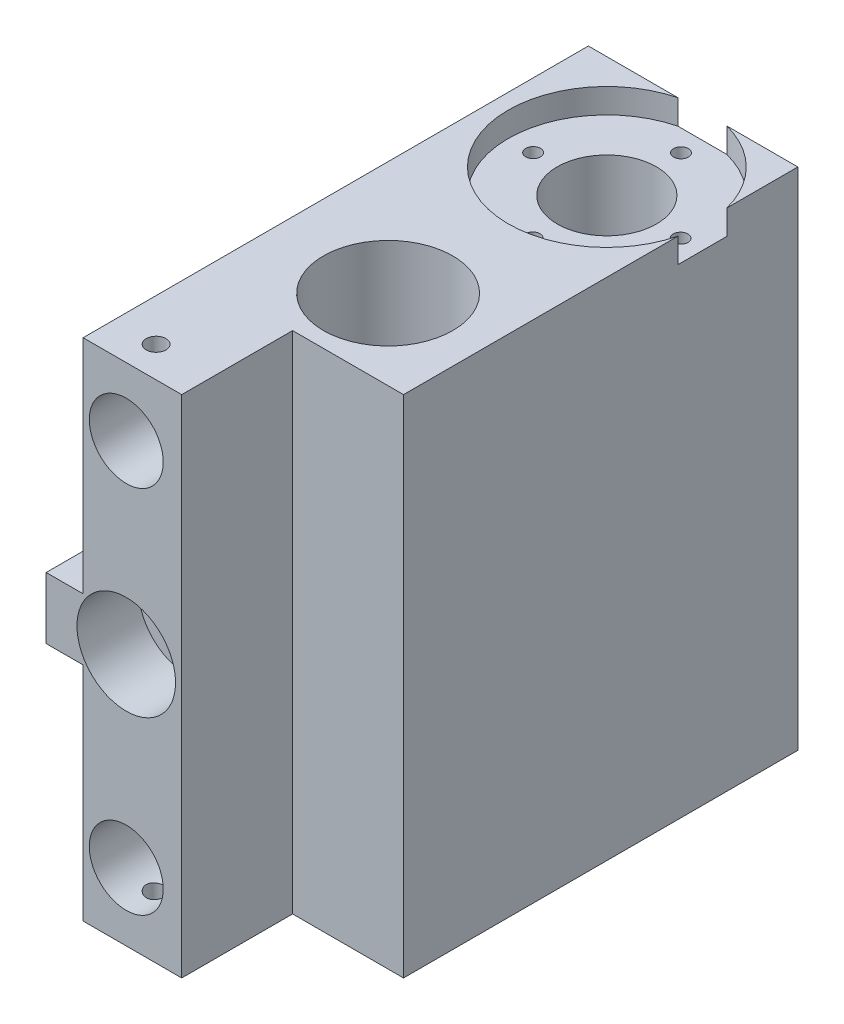
SolidWorks part; units mm, degrees
material "1060 Alloy"
ref_plane "Front Plane" through (0, 0, 0) normal (0, 0, 1) x (1, 0, 0)
ref_plane "Top Plane" through (0, 0, 0) normal (0, 1, 0) x (1, 0, 0)
ref_plane "Right Plane" through (0, 0, 0) normal (1, 0, 0) x (0, 0, -1)
sketch "Sketch1" plane through (0, 0, 0) normal (0, 0, 1) x (1, 0, 0)
  line L0 (-27, -6.0963) -> (-27, -75.9037) construction
  line L1 (0, 0) -> (-40, 0)
  line L2 (0, 0) -> (0, -82)
  line L3 (0, -82) -> (-40, -82)
  line L4 (-40, 0) -> (-40, -82)
  circle A0 centre (-27, -41) radius 5.5
  circle A1 centre (-27, -11) radius 6
  circle A2 centre (-27, -71) radius 6
  dimension "D3" = 11
  dimension "D4" = 12
  dimension "D5" = 12
  dimension "D1" = 40
  dimension "D2" = 82
  dimension "D6" = 11
  dimension "D7" = 30
  dimension "D8" = 13
  dimension "D9" = 30
  dimension "D10" = 11
extrude "Boss-Extrude1" add sketch "Sketch1" along normal blind 12
sketch "Sketch2" plane through (0, 0, 0) normal (0, 0, -1) x (-1, 0, 0)
  line L0 (0, -82) -> (0, 0) construction
  line L1 (40, -82) -> (0, -82) construction
  line L2 (40, 0) -> (40, -82) construction
  line L3 (0, 0) -> (40, 0) construction
  line L4 (0, -82) -> (0, 0)
  line L5 (40, -82) -> (0, -82)
  line L6 (40, 0) -> (40, -82)
  line L7 (0, 0) -> (40, 0)
  circle A0 centre (27, -41) radius 5.5 construction
  circle A1 centre (27, -41) radius 5.5
extrude "Boss-Extrude2" add sketch "Sketch2" along normal blind 70
sketch "Sketch3" plane through (0, 0, 0) normal (0, 1, 0) x (1, 0, 0)
  line L0 (-40, -5) -> (0, -5) construction
  line L1 (-40, -12) -> (-40, 70) construction
  line L2 (0, -12) -> (0, 70) construction
  line L3 (0, -12) -> (-40, -12) construction
  circle A0 centre (-27.1548, -7) radius 1.6
  dimension "D1" = 3.2
  dimension "D2" = 5
  dimension "D3" = 13
extrude "Cut-Extrude1" cut sketch "Sketch3" against normal blind 10
sketch "Sketch4" plane through (0, -82, 0) normal (0, -1, 0) x (1, 0, 0)
  circle A1 centre (-27.1548, 7) radius 1.6
  circle A2 centre (-27.1548, 7) radius 1.6
  dimension "D1" = 0
extrude "Cut-Extrude2" cut sketch "Sketch4" against normal blind 10
sketch "Sketch5" plane through (0, 0, 0) normal (0, 1, 0) x (1, 0, 0)
  line L0 (-15.5, 70) -> (-15.5, 49) construction
  line L1 (-40, 70) -> (0, 70) construction
  line L2 (0, -12) -> (-40, -12) construction
  line L3 (0, -12) -> (0, 70) construction
  line L4 (-15.5, 60) -> (-15.5, 49) construction
  line L5 (-15.5, 29.5) -> (-15.5, -12) construction
  line L6 (-15.5, 29.5) -> (-15.5, 8.5) construction
  circle A1 centre (-15.5, 19) radius 10.5
  circle A2 centre (-15.5, 54.5) radius 5.5
  dimension "D2" = 11
  dimension "D3" = 25
  dimension "D4" = 21
  dimension "D1" = 15.5
  dimension "D6" = 51
extrude "Cut-Extrude3" cut sketch "Sketch5" against normal blind 100
sketch "Sketch6" plane through (0, 0, 0) normal (0, 1, 0) x (1, 0, 0)
  circle A0 centre (-15.5, 54.5) radius 16
  dimension "D1" = 32
extrude "Cut-Extrude4" cut sketch "Sketch6" against normal blind 4
sketch "Sketch19" plane through (0, -4, 0) normal (0, 1, 0) x (1, 0, 0)
  circle A0 centre (-15.5, 54.5) radius 8.05
  dimension "D1" = 16.1
extrude "Cut-Extrude17" cut sketch "Sketch19" against normal blind 16
sketch "Sketch12" plane through (0, -4, 0) normal (0, 1, 0) x (1, 0, 0)
  line L1 (-3.5, 54.4698) -> (-3.4699, 66.4698) construction
  line L2 (-3.4699, 66.4698) -> (-15.4698, 66.5) construction
  line L3 (-27.5, 54.5302) -> (-27.5301, 42.5302) construction
  line L4 (-27.5301, 42.5302) -> (-15.5302, 42.5) construction
  circle A0 centre (-15.5, 54.5) radius 12 construction
  circle A1 centre (-15.5302, 42.5) radius 1.2
  circle A2 centre (-3.5, 54.4698) radius 1.2
  circle A3 centre (-15.4698, 66.5) radius 1.2
  circle A4 centre (-27.5, 54.5302) radius 1.2
  dimension "D1" = 24
  dimension "D2" = 2.4
extrude "Cut-Extrude12" cut sketch "Sketch12" against normal blind 12
sketch "Sketch13" plane through (0, 0, -70) normal (0, 0, -1) x (-1, 0, 0)
  line L1 (40, 0) -> (60, 0)
  line L2 (40, 0) -> (40, -70)
  line L3 (40, -70) -> (60, -70)
  line L4 (60, 0) -> (60, -70)
  dimension "D1" = 20
  dimension "D2" = 70
extrude "Boss-Extrude3" add sketch "Sketch13" against normal blind 30
sketch "Sketch14" plane through (0, 0, -70) normal (0, 0, -1) x (-1, 0, 0)
  line L1 (50.54, -17.46) -> (27, -17.46) construction
  line L2 (3.46, -41) -> (3.46, -64.54) construction
  line L3 (3.46, -64.54) -> (27, -64.54) construction
  line L4 (50.54, -41) -> (50.54, -17.46) construction
  circle A0 centre (27, -41) radius 23.54 construction
  circle A1 centre (50.54, -41) radius 2
  circle A2 centre (27, -17.46) radius 2
  circle A3 centre (3.46, -41) radius 2
  circle A4 centre (27, -64.54) radius 2
  dimension "D1" = 47.08
  dimension "D2" = 4
extrude "Cut-Extrude13" cut sketch "Sketch14" against normal blind 12
sketch "Sketch15" plane through (0, 0, -70) normal (0, 0, -1) x (-1, 0, 0)
  line L0 (34, 0) -> (34, -36)
  line L1 (60, 0) -> (19.4686, 0) construction
  line L2 (34, -36) -> (54.5811, -36)
  line L4 (34, -82) -> (34, -46)
  line L5 (0, -82) -> (40, -82) construction
  line L6 (34, -46) -> (54.5811, -46)
  line L7 (54.5811, -46) -> (54.5811, -36)
  line L8 (34, 0) -> (77.5206, 0)
  line L9 (77.5206, 0) -> (77.5206, -82)
  line L10 (77.5206, -82) -> (34, -82)
  line L11 (60, -70) -> (60, 0) construction
  dimension "D1" = 26
  dimension "D2" = 10
  dimension "D3" = 36
extrude "Cut-Extrude14" cut sketch "Sketch15" against normal blind 115
sketch "Sketch18" plane through (0, 0, -70) normal (0, 0, -1) x (-1, 0, 0)
  circle A0 centre (27, -41) radius 19.1
  dimension "D1" = 38.2
extrude "Cut-Extrude16" cut sketch "Sketch18" against normal blind 2
sketch "Sketch20" plane through (0, -82, 0) normal (0, -1, 0) x (1, 0, 0)
  line L1 (0, 12) -> (-18, 12)
  line L2 (0, 12) -> (0, -6)
  line L3 (0, -6) -> (-18, -6)
  line L4 (-18, 12) -> (-18, -6)
  dimension "D1" = 18
  dimension "D2" = 18
extrude "Cut-Extrude18" cut sketch "Sketch20" against normal blind 100
sketch "Sketch21" plane through (0, 0, 12) normal (0, 0, 1) x (1, 0, 0)
  circle A0 centre (-27, -41) radius 8
  dimension "D1" = 16
extrude "Cut-Extrude19" cut sketch "Sketch21" against normal blind 10
